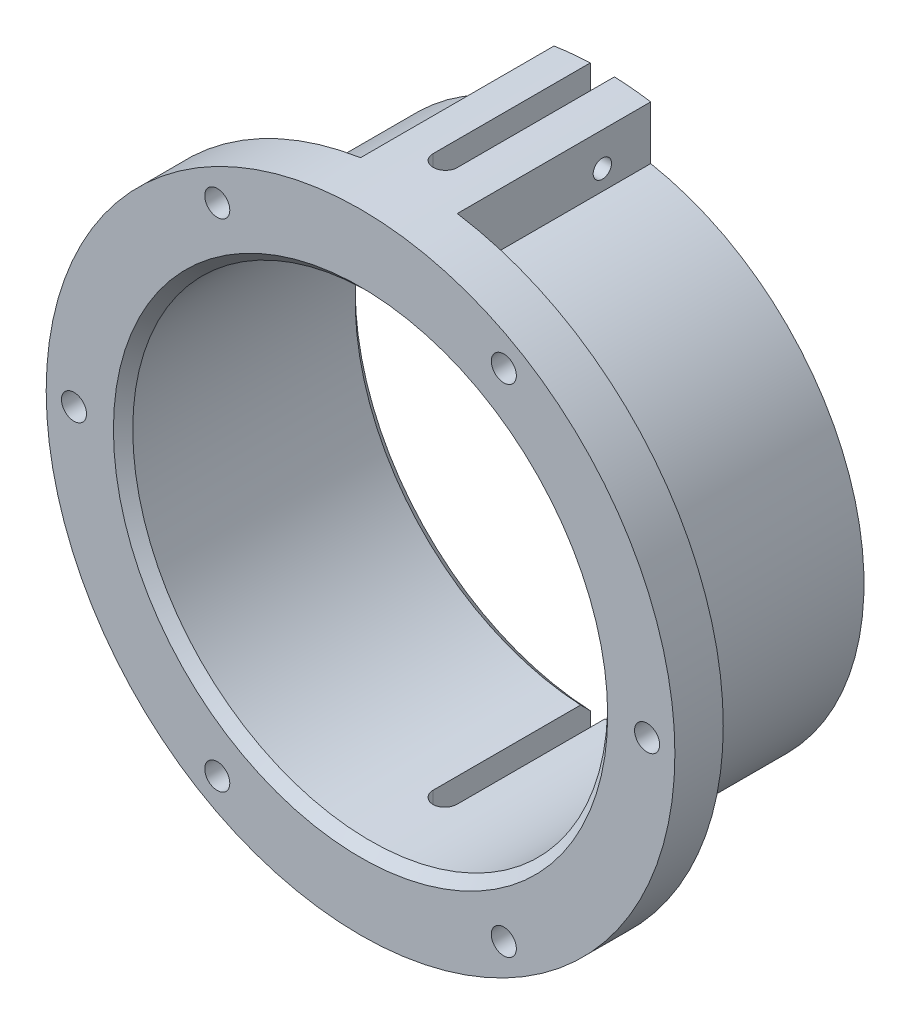
SolidWorks part; units mm, degrees
note: '?' marks a value the reader was unsure of.
material "6061 Alloy"
ref_plane "Front Plane" through (0, 0, 0) normal (0, 0, 1) x (1, 0, 0)
ref_plane "Top Plane" through (0, 0, 0) normal (0, 1, 0) x (1, 0, 0)
ref_plane "Right Plane" through (0, 0, 0) normal (1, 0, 0) x (0, 0, -1)
sketch "Sketch1" plane through (0, 0, 0) normal (1, 0, 0) x (0, 0, -1)
  line L0 (5, 49.1) -> (55, 49.1)
  line L1 (5, 49.1) -> (5, 65)
  line L2 (5, 65) -> (15, 65)
  line L3 (15, 65) -> (15, 54.1)
  line L4 (15, 54.1) -> (55, 54.1)
  line L5 (55, 49.1) -> (55, 54.1)
  line L6 (0, 0) -> (198.4792, 0) construction
  dimension "D1" = 49.1
  dimension "D2" = 50
  dimension "D3" = 5
  dimension "D4" = 10
  dimension "D5" = 65
  dimension "D6" = 5
revolve "Revolve1" add sketch "Sketch1" angle 360 about L6
sketch "Sketch2" plane through (0, 0, -15) normal (0, 0, -1) x (-1, 0, 0)
  line L0 (-10, 64.2262) -> (-10, 53.1678)
  line L1 (10, 64.2262) -> (10, 53.1678)
  line L2 (0, 0) -> (0, 105.9634) construction
  arc A0 (10, 53.1678) -> (-10, 53.1678) centre (0, 0) ccw
  circle A1 centre (0, 0) radius 65 construction
  arc A2 (-10, 64.2262) -> (10, 64.2262) centre (0, 0) cw
  circle A3 centre (0, 0) radius 54.1 construction
  dimension "D2" = 20
extrude "Boss-Extrude1" add sketch "Sketch2" along normal up to surface (40 mm away) up to face at (54.1, 0, -55)
ref_plane "Plane1" through (0, 0, 0) normal (0, 1, 0) x (1, 0, 0)
mirror "Mirror1" about plane through (0, 0, 0) normal (0, 1, 0) of "Boss-Extrude1"
sketch "Sketch3" plane through (0, 0, -55) normal (0, 0, -1) x (-1, 0, 0)
  line L0 (0, 0) -> (0, 26.8949) construction
  line L1 (-2.5, 67.8227) -> (2.5, 67.8227)
  line L2 (-2.5, 67.8227) -> (-2.5, -68.1773)
  line L3 (-2.5, -68.1773) -> (2.5, -68.1773)
  line L4 (2.5, 67.8227) -> (2.5, -68.1773)
  dimension "D1" = 5
  dimension "D2" = 136
extrude "Cut-Extrude1" cut sketch "Sketch3" against normal blind 35
fillet "Fillet1" radius 2.5 4 edges at (2.5, -56.9941, -20) (2.5, 56.9941, -20) (-2.5, -56.9941, -20) (-2.5, 56.9941, -20)
chamfer "Chamfer1" distance 2 angle 45 2 edges at (49.1, 0, -55) (-49.1, 0, -55)
chamfer "Chamfer2" distance 2 angle 45 1 edges at (49.1, 0, -5)
hole_wizard "#6 (0.204) Diameter Hole1" positions "Sketch4" profile "Sketch5" hole size "#6" standard "ANSI Inch"
sketch "Sketch4" plane through (0, 0, -5) normal (0, 0, 1) x (1, 0, 0)
  line L0 (0, 0) -> (-29.625, 51.312) construction
  line L2 (0, 0) -> (0, 59.25) construction
  circle A0 centre (0, 0) radius 59.25
  point P10 (-29.625, 51.312)
  dimension "D2" = 118.5
  dimension "D1" = 30
sketch "Sketch5" plane through (-29.625, 51.312, -5) normal (1, 0, 0) x (0, -1, 0)
  line L0 (0, 0) -> (0, 11.5557)
  line L1 (0, 11.5557) -> (2.5908, 9.999)
  line L2 (2.5908, 9.999) -> (2.5908, 0)
  line L5 (2.5908, 0) -> (0, 0)
  line L10 (0, 11.5557) -> (-2.5908, 9.999) construction
  line L11 (0, -6.35) -> (0, 107.95) construction
  dimension "Hole Dia." = 5.1816
  dimension "Hole Depth" = 9.999
  dimension "Drill Angle" = 118
ref_axis "Axis1" through (0, 0, -2.5) along (0, 0, -1)?
pattern_circular "CirPattern1" count 6 over 360 about axis through (0, 0, 0) along (0, 0, 1) of "#6 (0.204) Diameter Hole1"
hole_wizard "CBORE for #6 Binding Head Machine Screw1" positions "Sketch6" profile "Sketch8" counterbore size "#6" standard "ANSI Inch"
sketch "Sketch6" plane through (-10, 0, 0) normal (-1, 0, 0) x (0, 0, 1)
  line L0 (-55, -64.2262) -> (-55, -53.1678) construction
  line L2 (-55, -64.2262) -> (-15, -64.2262) construction
  point P0 (-45, -59.2262)
  dimension "D1" = 5
  dimension "D2" = 10
sketch "Sketch8" plane through (-10, -59.2262, -45) normal (0, 1, 0) x (0, 0, 1)
  line L0 (0, 0) -> (0, 26.1408)
  line L1 (0, 26.1408) -> (1.8986, 25)
  line L2 (1.8986, 25) -> (1.8986, 2.2098)
  line L3 (1.8986, 2.2098) -> (3.9687, 2.2098)
  line L4 (3.9687, 2.2098) -> (3.9687, 0)
  line L5 (3.9687, 0) -> (0, 0)
  line L10 (0, 26.1408) -> (-1.8987, 25) construction
  line L11 (0, -6.35) -> (0, 107.95) construction
  dimension "Hole Dia." = 3.7973
  dimension "Hole Depth" = 25
  dimension "C'Bore Dia." = 7.9375
  dimension "C'Bore Depth" = 2.2098
  dimension "Drill Angle" = 118
pattern_linear "LPattern1" count 2 spacing 116.5 along (0, 1, 0) of "CBORE for #6 Binding Head Machine Screw1"
equation "\"118.5.00mm\"=120"
